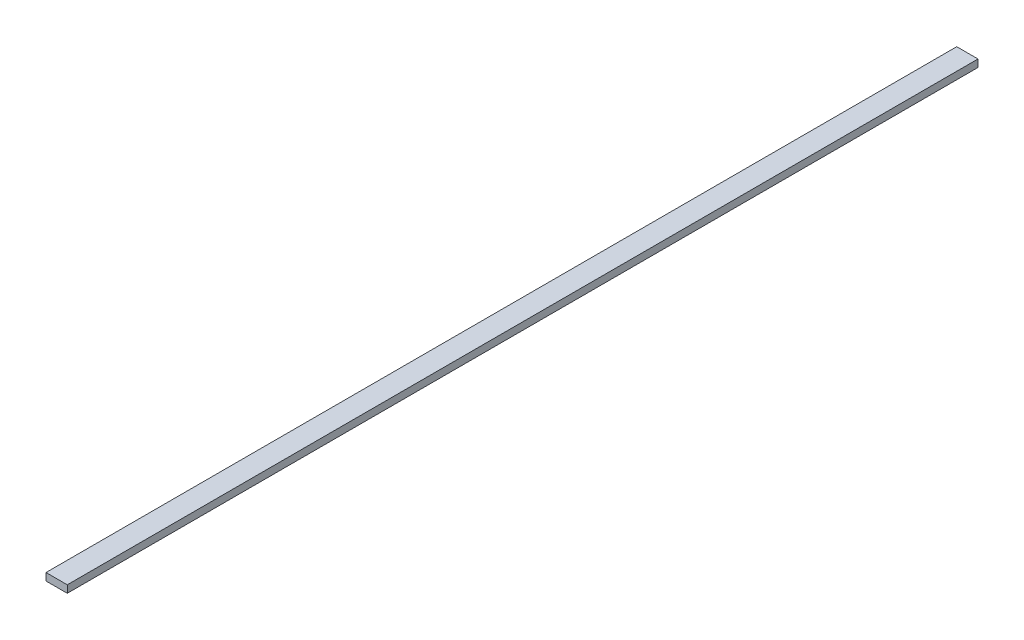
SolidWorks part; units mm, degrees
ref_plane "Front Plane" through (0, 0, 0) normal (0, 0, 1) x (1, 0, 0)
ref_plane "Top Plane" through (0, 0, 0) normal (0, 1, 0) x (1, 0, 0)
ref_plane "Right Plane" through (0, 0, 0) normal (1, 0, 0) x (0, 0, -1)
sketch "Sketch1" plane through (0, 0, 0) normal (0, 0, 1) x (1, 0, 0)
  line L1 (0, 0) -> (21.6, 0)
  line L2 (0, 0) -> (0, 7.5)
  line L3 (0, 7.5) -> (21.6, 7.5)
  line L4 (21.6, 0) -> (21.6, 7.5)
  dimension "D1" = 21.6
  dimension "D2" = 7.5
extrude "Boss-Extrude1" add sketch "Sketch1" along normal blind 925
equation "\"SlotWidth\"= 22mm"
equation "\"D1@Sketch1\"= \"SpacerWidth\""
equation "\"SpacerHeight\"= 7.5mm"
equation "\"D2@Sketch1\"= \"SpacerHeight\""
equation "\"AxialLength\"= 925mm"
equation "\"D1@Boss-Extrude1\"= \"AxialLength\""
equation "\"CarbonPaperThickness\"= 0.2mm"
equation "\"SpacerWidth\"= \"SlotWidth\" - \"CarbonPaperThickness\" * 2"
